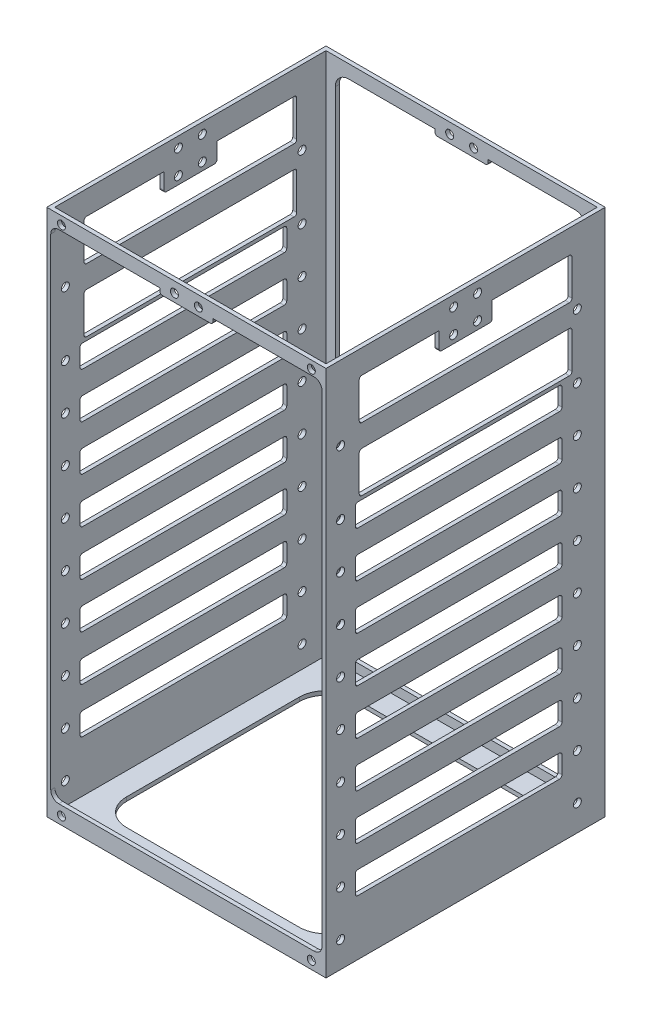
SolidWorks part; units mm, degrees
ref_plane "Front Plane" through (0, 0, 0) normal (0, 0, 1) x (1, 0, 0)
ref_plane "Top Plane" through (0, 0, 0) normal (0, 1, 0) x (1, 0, 0)
ref_plane "Right Plane" through (0, 0, 0) normal (1, 0, 0) x (0, 0, -1)
sketch "Sketch1" plane through (0, 0, 0) normal (0, 1, 0) x (1, 0, 0)
  line L1 (-52.5, -52.5) -> (52.5, -52.5)
  line L2 (-52.5, -52.5) -> (-52.5, 52.5)
  line L3 (-52.5, 52.5) -> (52.5, 52.5)
  line L4 (52.5, -52.5) -> (52.5, 52.5)
  line L5 (-52.5, -52.5) -> (52.5, 52.5) construction
  line L6 (-52.5, 52.5) -> (52.5, -52.5) construction
  line L7 (-32.5, -42.5) -> (32.5, -42.5)
  line L8 (-42.5, -32.5) -> (-42.5, 32.5)
  line L9 (-32.5, 42.5) -> (32.5, 42.5)
  line L10 (42.5, -32.5) -> (42.5, 32.5)
  line L11 (-42.5, -42.5) -> (42.5, 42.5) construction
  line L12 (-42.5, 42.5) -> (42.5, -42.5) construction
  arc A0 (32.5, -42.5) -> (42.5, -32.5) centre (32.5, -32.5) ccw
  arc A1 (32.5, 42.5) -> (42.5, 32.5) centre (32.5, 32.5) cw
  arc A2 (-42.5, 32.5) -> (-32.5, 42.5) centre (-32.5, 32.5) cw
  arc A3 (-32.5, -42.5) -> (-42.5, -32.5) centre (-32.5, -32.5) cw
  point P0 (0, 0)
  point P6 (0, 0)
  dimension "D3" = 10
  dimension "D1" = 105
  dimension "D2" = 42.5
extrude "Boss-Extrude2" add sketch "Sketch1" along normal blind 1.5 contours A3 L7 A0 L10 A1 L9 A2 L8 | L2 L1 L4 L3 region at (0, 0, 0)
sketch "Sketch3" plane through (0, 1.5, 0) normal (0, 1, 0) x (1, 0, 0)
  line L1 (-52.5, -52.5) -> (52.5, -52.5)
  line L2 (-52.5, -52.5) -> (-52.5, 52.5)
  line L3 (-52.5, 52.5) -> (52.5, 52.5)
  line L4 (52.5, -52.5) -> (52.5, 52.5)
  line L5 (-52.5, -52.5) -> (52.5, 52.5) construction
  line L6 (-52.5, 52.5) -> (52.5, -52.5) construction
  line L7 (-51, -51) -> (51, -51)
  line L8 (-51, -51) -> (-51, 51)
  line L9 (-51, 51) -> (51, 51)
  line L10 (51, -51) -> (51, 51)
  line L11 (-51, -51) -> (51, 51) construction
  line L12 (-51, 51) -> (51, -51) construction
  point P0 (0, 0)
  point P7 (0, 0)
  dimension "D1" = 1.5
extrude "Boss-Extrude3" add sketch "Sketch3" along normal blind 197 contours L8 L7 L10 L9 | L2 L3 L4 L1
sketch "Sketch4" plane through (0, 0, -52.5) normal (0, 0, 1) x (1, 0, 0)
  line L0 (-52.5, 0) -> (52.5, 0) construction
  line L1 (-42.5, 5) -> (42.5, 5)
  line L2 (-47.5, 10) -> (-47.5, 188.5)
  line L3 (-42.5, 193.5) -> (42.5, 193.5)
  line L4 (47.5, 10) -> (47.5, 188.5)
  line L5 (-47.5, 5) -> (47.5, 193.5) construction
  line L6 (-47.5, 193.5) -> (47.5, 5) construction
  line L7 (52.5, 198.5) -> (52.5, 0) construction
  line L8 (-51, 198.5) -> (51, 198.5) construction
  line L9 (-52.5, 198.5) -> (-52.5, 0) construction
  arc A0 (-42.5, 5) -> (-47.5, 10) centre (-42.5, 10) cw
  arc A1 (42.5, 5) -> (47.5, 10) centre (42.5, 10) ccw
  arc A2 (42.5, 193.5) -> (47.5, 188.5) centre (42.5, 188.5) cw
  arc A3 (-47.5, 188.5) -> (-42.5, 193.5) centre (-42.5, 188.5) cw
  point P0 (0, 99.25)
  dimension "D5" = 5
  dimension "D1" = 5
  dimension "D2" = 5
  dimension "D3" = 5
  dimension "D4" = 5
extrude "Cut-Extrude1" cut sketch "Sketch4" along normal up to surface (1.5 mm away) up to face at (0, 100, -51)
sketch "Sketch5" plane through (0, 0, 52.5) normal (0, 0, 1) x (1, 0, 0)
  line L0 (-52.5, 198.5) -> (52.5, 198.5) construction
  line L1 (-48, 6.5) -> (48, 6.5)
  line L2 (-51, 9.5) -> (-51, 190.5)
  line L3 (-48, 193.5) -> (48, 193.5)
  line L4 (51, 9.5) -> (51, 190.5)
  line L5 (-51, 6.5) -> (51, 193.5) construction
  line L6 (-51, 193.5) -> (51, 6.5) construction
  line L7 (-52.5, 1.5) -> (52.5, 1.5) construction
  line L8 (-52.5, 198.5) -> (-52.5, 0) construction
  line L9 (52.5, 198.5) -> (52.5, 0) construction
  arc A0 (48, 6.5) -> (51, 9.5) centre (48, 9.5) ccw
  arc A1 (-48, 6.5) -> (-51, 9.5) centre (-48, 9.5) cw
  arc A2 (48, 193.5) -> (51, 190.5) centre (48, 190.5) cw
  arc A3 (-51, 190.5) -> (-48, 193.5) centre (-48, 190.5) cw
  point P0 (0, 100)
  dimension "D5" = 3
  dimension "D1" = 5
  dimension "D2" = 5
  dimension "D3" = 1.5
  dimension "D4" = 1.5
sketch "Sketch6" plane through (52.5, 0, 0) normal (1, 0, 0) x (0, 0, -1)
  line L0 (-52.5, 6.5) -> (-52.5, 193.5) construction
  line L2 (-52.5, 0) -> (52.5, 0) construction
  circle A0 centre (-47, 9.75) radius 1.5
  circle A1 centre (42, 9.75) radius 1.5
  circle A2 centre (-47, 26.85) radius 1.5
  circle A3 centre (42, 26.85) radius 1.5
  circle A4 centre (-47, 43.95) radius 1.5
  circle A5 centre (42, 43.95) radius 1.5
  circle A6 centre (-47, 61.05) radius 1.5
  circle A7 centre (42, 61.05) radius 1.5
  circle A8 centre (-47, 78.15) radius 1.5
  circle A9 centre (42, 78.15) radius 1.5
  circle A10 centre (-47, 95.25) radius 1.5
  circle A11 centre (42, 95.25) radius 1.5
  circle A12 centre (-47, 112.35) radius 1.5
  circle A13 centre (42, 112.35) radius 1.5
  circle A14 centre (-47, 129.45) radius 1.5
  circle A15 centre (42, 129.45) radius 1.5
  circle A16 centre (-47, 146.55) radius 1.5
  circle A17 centre (42, 146.55) radius 1.5
  circle A18 centre (-47, 170.55) radius 1.5
  circle A19 centre (42, 170.55) radius 1.5
  dimension "D4" = 3
  dimension "D5" = 3
  dimension "D1" = 5.5
  dimension "D2" = 89
  dimension "D3" = 9.75
  dimension "D7" = 17.1
  dimension "D9" = 24
  dimension "D6" = 9
  dimension "D8" = 2
extrude "Cut-Extrude2" cut sketch "Sketch6" against normal through all
extrude "Cut-Extrude3" cut sketch "Sketch5" against normal up to surface (1.5 mm away) up to face at (0, 100, 51)
sketch "Sketch7" plane through (52.5, 0, 0) normal (1, 0, 0) x (0, 0, -1)
  line L0 (-41.5, 38.95) -> (-41.5, 45.45)
  line L1 (-40.5, 20.85) -> (35.25, 20.85)
  line L2 (-41.5, 21.85) -> (-41.5, 28.35)
  line L3 (-40.5, 29.35) -> (35.25, 29.35)
  line L4 (36.25, 21.85) -> (36.25, 28.35)
  line L5 (-41.5, 20.85) -> (36.25, 29.35) construction
  line L6 (-41.5, 29.35) -> (36.25, 20.85) construction
  line L8 (-40.5, 37.95) -> (35.25, 37.95)
  line L9 (36.25, 38.95) -> (36.25, 45.45)
  line L10 (-40.5, 46.45) -> (35.25, 46.45)
  line L11 (-41.5, 56.05) -> (-41.5, 62.55)
  line L12 (-40.5, 55.05) -> (35.25, 55.05)
  line L13 (36.25, 56.05) -> (36.25, 62.55)
  line L14 (-40.5, 63.55) -> (35.25, 63.55)
  line L15 (-41.5, 73.15) -> (-41.5, 79.65)
  line L16 (-40.5, 72.15) -> (35.25, 72.15)
  line L17 (36.25, 73.15) -> (36.25, 79.65)
  line L18 (-40.5, 80.65) -> (35.25, 80.65)
  line L19 (-41.5, 90.25) -> (-41.5, 96.75)
  line L20 (-40.5, 89.25) -> (35.25, 89.25)
  line L21 (36.25, 90.25) -> (36.25, 96.75)
  line L22 (-40.5, 97.75) -> (35.25, 97.75)
  line L23 (-41.5, 107.35) -> (-41.5, 113.85)
  line L24 (-40.5, 106.35) -> (35.25, 106.35)
  line L25 (36.25, 107.35) -> (36.25, 113.85)
  line L26 (-40.5, 114.85) -> (35.25, 114.85)
  line L27 (-41.5, 124.45) -> (-41.5, 130.95)
  line L28 (-40.5, 123.45) -> (35.25, 123.45)
  line L29 (36.25, 124.45) -> (36.25, 130.95)
  line L30 (-40.5, 131.95) -> (35.25, 131.95)
  line L31 (-41.5, 141.55) -> (-41.5, 148.05)
  line L32 (-40.5, 140.55) -> (35.25, 140.55)
  line L33 (36.25, 141.55) -> (36.25, 148.05)
  line L34 (-40.5, 149.05) -> (35.25, 149.05)
  circle A0 centre (-47, 9.75) radius 1.5 construction
  arc A1 (35.25, 29.35) -> (36.25, 28.35) centre (35.25, 28.35) cw
  arc A2 (35.25, 20.85) -> (36.25, 21.85) centre (35.25, 21.85) ccw
  arc A3 (-40.5, 20.85) -> (-41.5, 21.85) centre (-40.5, 21.85) cw
  arc A4 (-41.5, 28.35) -> (-40.5, 29.35) centre (-40.5, 28.35) cw
  arc A5 (-41.5, 45.45) -> (-40.5, 46.45) centre (-40.5, 45.45) cw
  arc A6 (-40.5, 37.95) -> (-41.5, 38.95) centre (-40.5, 38.95) cw
  arc A7 (35.25, 37.95) -> (36.25, 38.95) centre (35.25, 38.95) ccw
  arc A8 (35.25, 46.45) -> (36.25, 45.45) centre (35.25, 45.45) cw
  arc A9 (-41.5, 62.55) -> (-40.5, 63.55) centre (-40.5, 62.55) cw
  arc A10 (-40.5, 55.05) -> (-41.5, 56.05) centre (-40.5, 56.05) cw
  arc A11 (35.25, 55.05) -> (36.25, 56.05) centre (35.25, 56.05) ccw
  arc A12 (35.25, 63.55) -> (36.25, 62.55) centre (35.25, 62.55) cw
  arc A13 (-41.5, 79.65) -> (-40.5, 80.65) centre (-40.5, 79.65) cw
  arc A14 (-40.5, 72.15) -> (-41.5, 73.15) centre (-40.5, 73.15) cw
  arc A15 (35.25, 72.15) -> (36.25, 73.15) centre (35.25, 73.15) ccw
  arc A16 (35.25, 80.65) -> (36.25, 79.65) centre (35.25, 79.65) cw
  arc A17 (-41.5, 96.75) -> (-40.5, 97.75) centre (-40.5, 96.75) cw
  arc A18 (-40.5, 89.25) -> (-41.5, 90.25) centre (-40.5, 90.25) cw
  arc A19 (35.25, 89.25) -> (36.25, 90.25) centre (35.25, 90.25) ccw
  arc A20 (35.25, 97.75) -> (36.25, 96.75) centre (35.25, 96.75) cw
  arc A21 (-41.5, 113.85) -> (-40.5, 114.85) centre (-40.5, 113.85) cw
  arc A22 (-40.5, 106.35) -> (-41.5, 107.35) centre (-40.5, 107.35) cw
  arc A23 (35.25, 106.35) -> (36.25, 107.35) centre (35.25, 107.35) ccw
  arc A24 (35.25, 114.85) -> (36.25, 113.85) centre (35.25, 113.85) cw
  arc A25 (-41.5, 130.95) -> (-40.5, 131.95) centre (-40.5, 130.95) cw
  arc A26 (-40.5, 123.45) -> (-41.5, 124.45) centre (-40.5, 124.45) cw
  arc A27 (35.25, 123.45) -> (36.25, 124.45) centre (35.25, 124.45) ccw
  arc A28 (35.25, 131.95) -> (36.25, 130.95) centre (35.25, 130.95) cw
  arc A29 (-41.5, 148.05) -> (-40.5, 149.05) centre (-40.5, 148.05) cw
  arc A30 (-40.5, 140.55) -> (-41.5, 141.55) centre (-40.5, 141.55) cw
  arc A31 (35.25, 140.55) -> (36.25, 141.55) centre (35.25, 141.55) ccw
  arc A32 (35.25, 149.05) -> (36.25, 148.05) centre (35.25, 148.05) cw
  circle A35 centre (42, 9.75) radius 1.5 construction
  point P0 (-2.625, 25.1)
  dimension "D5" = 1
  dimension "D3" = 5.75
  dimension "D1" = 8.5
  dimension "D2" = 11.1
  dimension "D4" = 5.5
  dimension "D7" = 8.6
  dimension "D6" = 8
extrude "Cut-Extrude4" cut sketch "Sketch7" against normal through all
sketch "Sketch8" plane through (52.5, 0, 0) normal (1, 0, 0) x (0, 0, -1)
  line L1 (-39, 150.35) -> (39, 150.35)
  line L2 (-40, 151.35) -> (-40, 164.75)
  line L3 (-39, 165.75) -> (39, 165.75)
  line L4 (40, 151.35) -> (40, 164.75)
  line L5 (-40, 150.35) -> (40, 165.75) construction
  line L6 (-40, 165.75) -> (40, 150.35) construction
  line L7 (52.5, 198.5) -> (52.5, 0) construction
  line L8 (-40, 189.55) -> (40, 174.15) construction
  line L9 (-40, 175.15) -> (-40, 188.55)
  line L10 (-39, 174.15) -> (39, 174.15)
  line L11 (40, 175.15) -> (40, 188.55)
  line L12 (-39, 189.55) -> (39, 189.55)
  circle A0 centre (-47, 146.55) radius 1.5 construction
  arc A2 (-40, 164.75) -> (-39, 165.75) centre (-39, 164.75) cw
  arc A3 (39, 165.75) -> (40, 164.75) centre (39, 164.75) cw
  arc A4 (39, 150.35) -> (40, 151.35) centre (39, 151.35) ccw
  arc A5 (-39, 150.35) -> (-40, 151.35) centre (-39, 151.35) cw
  arc A6 (-39, 174.15) -> (-40, 175.15) centre (-39, 175.15) cw
  arc A7 (-40, 188.55) -> (-39, 189.55) centre (-39, 188.55) cw
  arc A8 (39, 174.15) -> (40, 175.15) centre (39, 175.15) ccw
  arc A9 (39, 189.55) -> (40, 188.55) centre (39, 188.55) cw
  point P0 (0, 158.05)
  dimension "D5" = 1
  dimension "D1" = 3.8
  dimension "D2" = 15.4
  dimension "D3" = 80
  dimension "D4" = 12.5
  dimension "D7" = 8.4
  dimension "D6" = 2
extrude "Cut-Extrude5" cut sketch "Sketch8" against normal through all
sketch "Sketch15" plane through (52.5, 0, 0) normal (1, 0, 0) x (0, 0, -1)
  line L0 (39, 189.55) -> (-39, 189.55) construction
  line L1 (-10, 189.55) -> (10, 189.55)
  line L2 (-10, 189.55) -> (-10, 183.55)
  line L3 (-9, 182.55) -> (9, 182.55)
  line L4 (10, 189.55) -> (10, 183.55)
  line L5 (-52.5, 198.5) -> (-52.5, 0) construction
  arc A0 (9, 182.55) -> (10, 183.55) centre (9, 183.55) ccw
  arc A1 (-10, 183.55) -> (-9, 182.55) centre (-9, 183.55) ccw
  dimension "D4" = 1
  dimension "D1" = 20
  dimension "D2" = 7
  dimension "D3" = 42.5
extrude "Boss-Extrude4" add sketch "Sketch15" against normal up to surface (1.5 mm away) up to face at (51, 158.05, 0)
sketch "Sketch16" plane through (-52.5, 0, 0) normal (-1, 0, 0) x (0, 0, 1)
  line L1 (-10, 189.55) -> (10, 189.55)
  line L2 (-10, 189.55) -> (-10, 183.55)
  line L3 (-9, 182.55) -> (9, 182.55)
  line L4 (10, 189.55) -> (10, 183.55)
  arc A0 (9, 182.55) -> (10, 183.55) centre (9, 183.55) ccw
  arc A1 (-10, 183.55) -> (-9, 182.55) centre (-9, 183.55) ccw
  dimension "D3" = 1
  dimension "D1" = 7
  dimension "D2" = 20
extrude "Boss-Extrude5" add sketch "Sketch16" against normal up to surface (1.5 mm away) up to face at (-51, 158.05, 0)
sketch "Sketch9" plane through (52.5, 0, 0) normal (1, 0, 0) x (0, 0, -1)
  line L0 (-52.5, 198.5) -> (52.5, 198.5) construction
  line L1 (-52.5, 198.5) -> (-52.5, 0) construction
  line L2 (-10.0428, 190) -> (10.2919, 190) construction
  circle A0 centre (-4.5, 194.5) radius 1.5
  circle A1 centre (4.5, 194.5) radius 1.5
  circle A2 centre (4.5, 185.5) radius 1.5
  circle A3 centre (-4.5, 185.5) radius 1.5
  dimension "D1" = 3
  dimension "D3" = 9
  dimension "D5" = 3
  dimension "D2" = 4
  dimension "D4" = 48
  dimension "D6" = 4.5
extrude "Cut-Extrude6" cut sketch "Sketch9" against normal through all
sketch "Sketch17" plane through (0, 0, 52.5) normal (0, 0, 1) x (1, 0, 0)
  line L0 (48, 193.5) -> (-48, 193.5) construction
  line L1 (-10, 193.5) -> (10, 193.5)
  line L2 (-10, 193.5) -> (-10, 192.5)
  line L3 (-9, 191.5) -> (9, 191.5)
  line L4 (10, 193.5) -> (10, 192.5)
  line L5 (-52.5, 198.5) -> (-52.5, 0) construction
  arc A0 (9, 191.5) -> (10, 192.5) centre (9, 192.5) ccw
  arc A1 (-10, 192.5) -> (-9, 191.5) centre (-9, 192.5) ccw
  dimension "D4" = 1
  dimension "D1" = 20
  dimension "D2" = 42.5
  dimension "D3" = 2
extrude "Boss-Extrude6" add sketch "Sketch17" against normal up to surface (1.5 mm away) up to face at (0, 194.3738, 51)
sketch "Sketch18" plane through (0, 0, -52.5) normal (0, 0, -1) x (-1, 0, 0)
  line L1 (-10, 193.5) -> (10, 193.5)
  line L2 (-10, 193.5) -> (-10, 192.5)
  line L3 (-9, 191.5) -> (9, 191.5)
  line L4 (10, 193.5) -> (10, 192.5)
  arc A0 (9, 191.5) -> (10, 192.5) centre (9, 192.5) ccw
  arc A1 (-10, 192.5) -> (-9, 191.5) centre (-9, 192.5) ccw
  dimension "D3" = 1
  dimension "D1" = 2
  dimension "D2" = 20
extrude "Boss-Extrude7" add sketch "Sketch18" against normal up to surface (1.5 mm away) up to face at (0, 99.25, -51)
sketch "Sketch19" plane through (0, 0, 52.5) normal (0, 0, 1) x (1, 0, 0)
  line L0 (0, 198.5) -> (0, 191.5) construction
  line L1 (-9, 191.5) -> (9, 191.5) construction
  line L3 (-52.5, 198.5) -> (52.5, 198.5) construction
  circle A0 centre (-4.5, 194.5) radius 1.5
  circle A1 centre (4.5, 194.5) radius 1.5
  dimension "D1" = 3
  dimension "D2" = 4
  dimension "D3" = 4.5
extrude "Cut-Extrude7" cut sketch "Sketch19" against normal through all
sketch "Sketch20" plane through (0, 0, 52.5) normal (0, 0, 1) x (1, 0, 0)
  line L0 (-52.5, 198.5) -> (-52.5, 0) construction
  line L1 (-52.5, 0) -> (52.5, 0) construction
  line L2 (0, 198.5) -> (0, 0) construction
  line L3 (-52.5, 198.5) -> (52.5, 198.5) construction
  circle A0 centre (-46.98, 3) radius 1.5
  circle A1 centre (-46.98, 195.5) radius 1.5
  circle A2 centre (46.98, 3) radius 1.5
  circle A3 centre (46.98, 195.5) radius 1.5
  dimension "D1" = 3
  dimension "D4" = 3
  dimension "D2" = 5.52
  dimension "D3" = 3
  dimension "D5" = 5.52
  dimension "D6" = 3
extrude "Cut-Extrude8" cut sketch "Sketch20" against normal up to surface (1.5 mm away) up to face at (-6, 194.5, 51)
